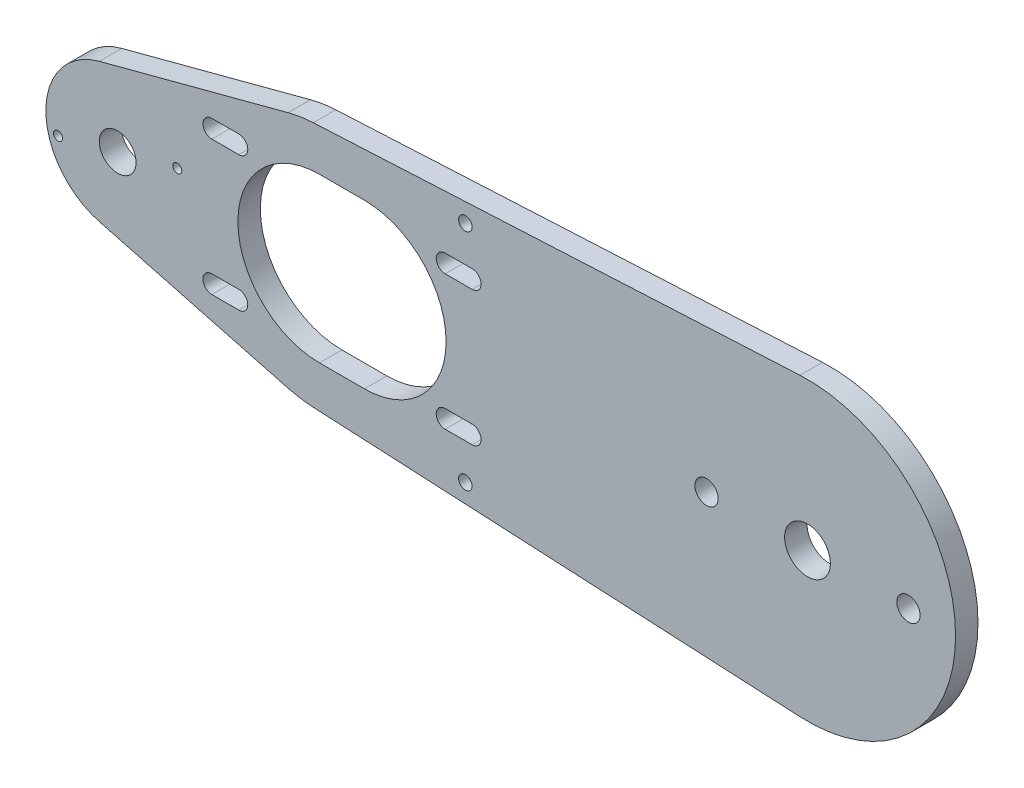
SolidWorks part; units mm, degrees
ref_plane "Front Plane" through (0, 0, 0) normal (0, 0, 1) x (1, 0, 0)
ref_plane "Top Plane" through (0, 0, 0) normal (0, 1, 0) x (1, 0, 0)
ref_plane "Right Plane" through (0, 0, 0) normal (1, 0, 0) x (0, 0, -1)
sketch "Sketch1" plane through (0, 0, 0) normal (0, 0, 1) x (1, 0, 0)
  line L0 (-51.875, 0) -> (51.875, 0) construction
  line L3 (-58.2658, 27.4648) -> (50.206, 32.9578)
  line L4 (-58.2658, -27.4648) -> (50.206, -32.9578)
  line L5 (-46.875, 0) -> (-56.875, 0) construction
  line L6 (-46.875, -18.2) -> (-56.875, -18.2)
  line L7 (-46.875, 18.2) -> (-56.875, 18.2)
  line L8 (-51.875, 0) -> (-101.875, 0) construction
  line L9 (-105.9639, 15.4687) -> (-63.9028, 26.5868)
  line L10 (-105.9639, -15.4687) -> (-63.9028, -26.5868)
  arc A3 (50.206, -32.9578) -> (50.206, 32.9578) centre (51.875, 0) ccw
  circle A5 centre (51.875, 0) radius 5.1
  arc A6 (-46.875, -18.2) -> (-46.875, 18.2) centre (-46.875, 0) ccw
  arc A7 (-56.875, 18.2) -> (-56.875, -18.2) centre (-56.875, 0) ccw
  arc A8 (-58.2658, 27.4648) -> (-63.9028, 26.5868) centre (-56.875, 0) ccw
  arc A9 (-105.9639, 15.4687) -> (-105.9639, -15.4687) centre (-101.875, 0) ccw
  circle A10 centre (-101.875, 0) radius 4.1
  arc A11 (-63.9028, -26.5868) -> (-58.2658, -27.4648) centre (-56.875, 0) ccw
  point P9 (-51.875, 0)
  dimension "D2" = 66
  dimension "D3" = 32
  dimension "D5" = 10.2
  dimension "D7" = 18.2
  dimension "D8" = 55
  dimension "D9" = 8.2
  dimension "D4" = 51.875
  dimension "D6" = 10
  dimension "D10" = 50
  dimension "D11" = 103.75
extrude "Boss-Extrude1" add sketch "Sketch1" along normal blind 5 contours L9 A9 L10 A8 A10 | L3 A8 L4 A3 A5 A7 L7 A6 L6 region at (-2.0915, 0, 0)
sketch "Sketch7" plane through (0, 0, 5) normal (0, 0, 1) x (1, 0, 0)
  line L0 (51.875, 5) -> (51.875, -5) construction
  line L1 (51.875, 0) -> (29.375, 0) construction
  circle A0 centre (51.875, 0) radius 5 construction
  circle A1 centre (29.375, 0) radius 2.6
  circle A2 centre (74.375, 0) radius 2.6
  dimension "D1" = 5.2
  dimension "D2" = 22.5
extrude "Cut-Extrude1" cut sketch "Sketch7" against normal blind 7
sketch "Sketch8" plane through (0, 0, 5) normal (0, 0, 1) x (1, 0, 0)
  line L0 (-84.375, 0) -> (-24.375, 0) construction
  line L1 (-24.375, 0) -> (-24.375, 25) construction
  line L3 (-28.9938, 25) -> (-26.6844, 21)
  line L4 (-26.6844, 21) -> (-22.0656, 21)
  line L5 (-22.0656, 21) -> (-19.7562, 25)
  line L6 (-19.7562, 25) -> (-22.0656, 29)
  line L7 (-22.0656, 29) -> (-26.6844, 29)
  line L8 (-26.6844, 29) -> (-28.9938, 25)
  line L9 (-25.775, 27.4249) -> (-27.175, 25)
  line L10 (-27.175, 25) -> (-25.775, 22.5751)
  line L11 (-25.775, 22.5751) -> (-22.975, 22.5751)
  line L12 (-22.975, 22.5751) -> (-21.575, 25)
  line L13 (-21.575, 25) -> (-22.975, 27.4249)
  line L14 (-22.975, 27.4249) -> (-25.775, 27.4249)
  arc A0 (-58.2658, 27.4648) -> (-58.2658, -27.4648) centre (-56.875, 0) ccw construction
  circle A2 centre (-24.375, 25) radius 4 construction
  circle A3 centre (-24.375, 25) radius 2.4249 construction
  point P6 (-24.375, 21)
  dimension "D1" = 8
  dimension "D2" = 5.6
  dimension "D3" = 25
  dimension "D4" = 60
extrude "Boss-Extrude7" add sketch "Sketch8" against normal blind 8
sketch "Sketch9" plane through (0, 0, 5) normal (0, 0, 1) x (1, 0, 0)
  line L0 (-24.375, 27.4249) -> (-24.375, 22.5751) construction
  line L1 (-22.975, 27.4249) -> (-25.775, 27.4249) construction
  line L2 (-25.775, 22.5751) -> (-22.975, 22.5751) construction
  circle A0 centre (-24.375, 25) radius 1.5
  dimension "D1" = 3
extrude "Cut-Extrude2" cut sketch "Sketch9" against normal blind 7
mirror "Mirror2" about plane through (0, 0, 0) normal (0, 1, 0) of "Cut-Extrude2"
sketch "Sketch10" plane through (0, 0, 5) normal (0, 0, 1) x (1, 0, 0)
  line L0 (-51.875, 18.2) -> (-51.875, -18.2) construction
  line L1 (-46.875, 18.2) -> (-56.875, 18.2) construction
  line L2 (-46.875, -18.2) -> (-56.875, -18.2) construction
  line L3 (-80.875, 15) -> (-74.875, 15) construction
  line L6 (-25.875, -15) -> (-77.875, -15) construction
  line L7 (-25.875, -15) -> (-25.875, 15) construction
  line L10 (-25.875, 15) -> (-77.875, 15) construction
  line L13 (-77.875, -15) -> (-77.875, 15) construction
  line L14 (-25.875, -15) -> (-77.875, 15) construction
  line L15 (-25.875, 15) -> (-77.875, -15) construction
  line L16 (-80.875, 17) -> (-74.875, 17)
  line L17 (-80.875, 13) -> (-74.875, 13)
  line L18 (-51.875, 0) -> (-77.875, 0) construction
  line L19 (-22.875, 15) -> (-28.875, 15) construction
  line L20 (-22.875, 17) -> (-28.875, 17)
  line L21 (-22.875, 13) -> (-28.875, 13)
  line L22 (-22.875, -15) -> (-28.875, -15) construction
  line L23 (-22.875, -17) -> (-28.875, -17)
  line L24 (-22.875, -13) -> (-28.875, -13)
  line L25 (-80.875, -15) -> (-74.875, -15) construction
  line L26 (-80.875, -17) -> (-74.875, -17)
  line L27 (-80.875, -13) -> (-74.875, -13)
  arc A7 (-80.875, 17) -> (-80.875, 13) centre (-80.875, 15) ccw
  arc A8 (-74.875, 13) -> (-74.875, 17) centre (-74.875, 15) ccw
  arc A9 (-22.875, 17) -> (-22.875, 13) centre (-22.875, 15) cw
  arc A10 (-28.875, 13) -> (-28.875, 17) centre (-28.875, 15) cw
  arc A11 (-22.875, -17) -> (-22.875, -13) centre (-22.875, -15) ccw
  arc A12 (-28.875, -13) -> (-28.875, -17) centre (-28.875, -15) ccw
  arc A13 (-80.875, -17) -> (-80.875, -13) centre (-80.875, -15) cw
  arc A14 (-74.875, -13) -> (-74.875, -17) centre (-74.875, -15) cw
  point P6 (-51.875, 0)
  point P13 (-77.875, 15)
  point P23 (-25.875, 15)
  point P30 (-25.875, -15)
  point P37 (-77.875, -15)
  dimension "D1" = 52
  dimension "D2" = 30
  dimension "D3" = 2
  dimension "D4" = 6
extrude "Cut-Extrude3" cut sketch "Sketch10" against normal blind 10 contours L17 A8 L16 A7 | A14 L27 A13 L26 | L24 A12 L23 A11 | A10 L21 A9 L20
sketch "Sketch11" plane through (0, 0, 5) normal (0, 0, 1) x (1, 0, 0)
  line L0 (-101.875, 0) -> (-117.875, 0) construction
  line L1 (-101.875, 0) -> (-115.1682, -3.5147) construction
  line L2 (-101.875, 0) -> (-105.3897, 13.2932) construction
  arc A0 (-105.9639, 15.4687) -> (-105.9639, -15.4687) centre (-101.875, 0) ccw construction
  circle A1 centre (-101.875, 0) radius 13.75 construction
  circle A2 centre (-115.1682, -3.5147) radius 1
  circle A3 centre (-88.5818, 3.5147) radius 1
  dimension "D1" = 27.5
  dimension "D2" = 2
  dimension "D3" = 14.81
extrude "Cut-Extrude4" cut sketch "Sketch11" against normal blind 10
sketch "Sketch12" plane through (0, 0, 0) normal (0, 0, -1) x (-1, 0, 0)
  line L0 (105.9639, 15.4687) -> (63.9028, 26.5868) construction
  line L1 (105.9639, -15.4687) -> (63.9028, -26.5868) construction
  line L2 (58.2658, -27.4648) -> (-50.206, -32.9578) construction
  line L3 (58.2658, 27.4648) -> (-50.206, 32.9578) construction
  line L4 (105.9639, 15.4687) -> (63.9028, 26.5868)
  line L5 (105.9639, -15.4687) -> (63.9028, -26.5868)
  line L6 (58.2658, -27.4648) -> (-50.206, -32.9578)
  line L7 (58.2658, 27.4648) -> (-50.206, 32.9578)
  arc A0 (63.9028, 26.5868) -> (58.2658, 27.4648) centre (56.875, 0) ccw construction
  arc A1 (105.9639, -15.4687) -> (105.9639, 15.4687) centre (101.875, 0) ccw construction
  arc A2 (58.2658, -27.4648) -> (63.9028, -26.5868) centre (56.875, 0) ccw construction
  arc A3 (-50.206, 32.9578) -> (-50.206, -32.9578) centre (-51.875, 0) ccw construction
  arc A4 (63.9028, 26.5868) -> (58.2658, 27.4648) centre (56.875, 0) ccw
  arc A5 (105.9639, -15.4687) -> (105.9639, 15.4687) centre (101.875, 0) ccw
  arc A6 (58.2658, -27.4648) -> (63.9028, -26.5868) centre (56.875, 0) ccw
  arc A7 (-50.206, 32.9578) -> (-50.206, -32.9578) centre (-51.875, 0) ccw
extrude "Cut-Extrude5" cut sketch "Sketch12" along normal blind 5
